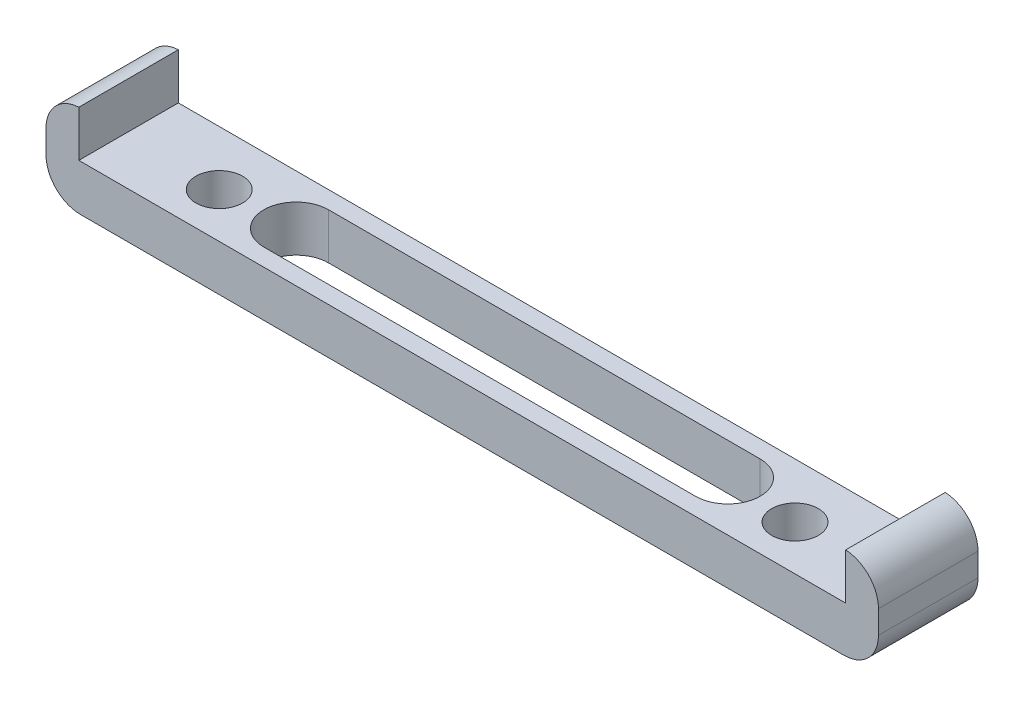
SolidWorks part; units mm, degrees
ref_plane "Front Plane" through (0, 0, 0) normal (0, 0, 1) x (1, 0, 0)
ref_plane "Top Plane" through (0, 0, 0) normal (0, 1, 0) x (1, 0, 0)
ref_plane "Right Plane" through (0, 0, 0) normal (1, 0, 0) x (0, 0, -1)
sketch "Sketch1" plane through (0, 0, 0) normal (0, 1, 0) x (1, 0, 0)
  line L0 (0, 0) -> (66.29, 0)
  line L1 (66.29, 0) -> (66.29, 100)
  line L2 (66.29, 100) -> (0, 100)
  line L3 (0, 100) -> (0, 0)
extrude "Boss-Extrude1" add sketch "Sketch1" along normal blind 41.59
shell "Shell2" thickness 3
sketch "Sketch3" plane through (0, 0, 0) normal (0, 0, 1) x (1, 0, 0)
  line L1 (0, 41.59) -> (66.29, 41.59) construction
  line L2 (54.395, 15) -> (11.895, 15)
  line L3 (11.895, 15) -> (11.895, 31.32)
  line L4 (11.895, 31.32) -> (8.815, 31.32)
  line L5 (8.815, 31.32) -> (8.815, 33.97)
  line L8 (7.145, 35.32) -> (7.755, 35.32)
  line L9 (7.755, 35.32) -> (8.815, 33.97)
  line L10 (7.145, 35.32) -> (7.145, 41.59)
  line L11 (7.145, 41.59) -> (59.145, 41.59)
  line L12 (57.145, 35.32) -> (59.145, 41.59)
  line L13 (57.145, 35.32) -> (56.535, 35.32)
  line L14 (56.535, 35.32) -> (55.475, 33.97)
  line L15 (55.475, 31.32) -> (55.475, 33.97)
  line L16 (52.395, 31.32) -> (55.475, 31.32)
  line L17 (54.395, 15) -> (52.395, 31.32)
  line L18 (33.145, 15) -> (33.145, 41.59) construction
  line L23 (0, 0) -> (66.29, 0)
  line L24 (66.29, 0) -> (66.29, 41.59)
  line L25 (66.29, 41.59) -> (0, 41.59)
  line L26 (0, 41.59) -> (0, 0)
  line L27 (0, 0) -> (66.29, 0) construction
  line L28 (66.29, 0) -> (66.29, 41.59) construction
  line L29 (66.29, 41.59) -> (0, 41.59) construction
  line L30 (0, 41.59) -> (0, 0) construction
  point P0 (33.145, 41.59)
  point P1 (33.145, 15)
  point P22 (33.145, 0)
  dimension "D1" = 16.32
  dimension "D2" = 21.25
  dimension "D3" = 0
  dimension "D4" = 2.65
  dimension "D5" = 1.35
  dimension "D6" = 1.06
  dimension "D7" = 0.61
  dimension "D8" = 3.08
  dimension "D9" = 26.59
extrude "Cut-Extrude1" cut sketch "Sketch3" against normal blind 125.59
fillet "Fillet1" radius 2 8 edges at (33.145, 0, 0) (33.145, 0, -100) (0, 20.795, -100) (66.29, 20.795, -100) (0, 20.795, 0) (66.29, 20.795, 0) (66.29, 0, -50) (0, 0, -50)
sketch "Sketch5" plane through (0, 0, 0) normal (-1, 0, 0) x (0, 0, 1)
  line L0 (-98, 0) -> (-2, 0) construction
  line L1 (-72.87, 8) -> (-90.37, 8) construction
  line L2 (-100, 8) -> (-72.87, 8) construction
  line L3 (-100, 2) -> (-100, 41.59) construction
  line L5 (-90.37, 8) -> (-90.37, 15.93) construction
  line L6 (-72.87, 8) -> (-72.87, 19.0845) construction
  circle A0 centre (-72.87, 8) radius 5
  circle A1 centre (-90.37, 15.93) radius 2.32
  circle A2 centre (-55.37, 15.93) radius 2.32
  dimension "D3" = 17.5
  dimension "D1" = 8
  dimension "D2" = 27.13
extrude "Cut-Extrude2" cut sketch "Sketch5" against normal up to surface (66.29 mm away) contours A0 | A1 | A2 up to face at (66.29, 21.795, -50)
sketch "Sketch6" plane through (0, 0, 0) normal (-1, 0, 0) x (0, 0, 1)
  line L0 (-72.87, 8) -> (-72.87, 0) construction
  line L1 (-98, 0) -> (-2, 0) construction
  line L2 (-72.87, 0) -> (-72.87, 25.24) construction
  circle A0 centre (-72.87, 25.24) radius 23.17
extrude "Cut-Extrude3" cut sketch "Sketch6" along direction (1, 0, 0) on the side against the normal up to surface (60.29 mm away) from offset 3 contours A0 offset against normal yes
sketch "Sketch7" plane through (0, 0, 0) normal (-1, 0, 0) x (0, 0, 1)
  circle A0 centre (-55.37, 15.93) radius 3.7
  circle A1 centre (-90.37, 15.93) radius 3.7
extrude "Cut-Extrude4" cut sketch "Sketch7" against normal blind 1 contours A1 | A0
ref_plane "Plane1" through (33.145, 0, 0) normal (-1, 0, 0) x (0, 0, 1)
sketch "Sketch8" plane through (0, 3, 0) normal (0, 1, 0) x (1, 0, 0)
  line L0 (3, 2) -> (3, 21.25)
  line L1 (3, 66.3714) -> (3, 2) construction
  line L2 (3, 21.25) -> (15.79, 21.25) construction
  line L3 (15.79, 21.25) -> (15.79, 18.5)
  line L4 (15.79, 18.5) -> (13, 18.5)
  line L5 (13, 18.5) -> (13, 2)
  line L6 (3, 2) -> (63.29, 2) construction
  line L7 (15.79, 21.25) -> (8, 21.25)
  line L8 (8, 21.25) -> (8, 18.5)
  line L9 (8, 18.5) -> (3, 18.5)
  line L10 (3, 2) -> (13, 2)
  line M9 (3, 2) -> (63.29, 2)
  dimension "D1" = 12.79
  dimension "D2" = 2.79
  dimension "D3" = 2.75
  dimension "D4" = 7.79
  dimension "D5" = 16.5
extrude "Boss-Extrude2" add sketch "Sketch8" along normal blind 10 contours L8 L9 L0 L5 L4 L3 L7 M9
sketch "Sketch9" plane through (0, 0, 0) normal (-1, 0, 0) x (0, 0, 1)
  line L0 (0, 8) -> (-8.24, 8) construction
  line L1 (-8.24, 0) -> (-8.24, 8) construction
  line L2 (-98, 0) -> (-2, 0) construction
  circle A0 centre (-8.24, 8) radius 1.5
  dimension "D1" = 8.24
  dimension "D2" = 8
extrude "Cut-Extrude5" cut sketch "Sketch9" against normal up to surface (13 mm away) up to face at (13, 8, -10.25)
sketch "Sketch10" plane through (13, 0, 0) normal (1, 0, 0) x (0, 0, -1)
  line L1 (11.24, 8) -> (9.74, 10.5981)
  line L2 (9.74, 10.5981) -> (6.74, 10.5981)
  line L3 (6.74, 10.5981) -> (5.24, 8)
  line L4 (2, 3) -> (18.5, 3)
  line L5 (18.5, 3) -> (18.5, 13)
  line L6 (18.5, 13) -> (2, 13)
  line L7 (2, 13) -> (2, 3)
  line L8 (2, 3) -> (18.5, 3)
  line L9 (18.5, 3) -> (18.5, 13)
  line L10 (18.5, 13) -> (2, 13)
  line L11 (2, 13) -> (2, 3)
  line L12 (5.24, 8) -> (6.74, 5.4019)
  line L13 (6.74, 5.4019) -> (9.74, 5.4019)
  line L14 (9.74, 5.4019) -> (11.24, 8)
  circle A0 centre (8.24, 8) radius 1.5 construction
  circle A1 centre (8.24, 8) radius 1.5
  circle A2 centre (8.24, 8) radius 2.5981 construction
  circle M6 centre (8.24, 8) radius 1.5
  dimension "D2" = 3
  dimension "D1" = 0
extrude "Cut-Extrude6" cut sketch "Sketch10" against normal blind 6 contours L13 L14 L1 L2 L3 L12 M6 | M6
chamfer "Chamfer1" distance 1 angle 45 11 edges at (13, 8, -2) (3, 8, -18.5) (8, 8, -18.5) (11.895, 13, -21.25) (15.79, 13, -19.875) (14.395, 13, -18.5) (13, 13, -10.25) (8, 13, -2) (3, 13, -10.25) (5.5, 13, -18.5) (8, 13, -19.875)
sketch "Sketch11" plane through (0, 3, 0) normal (0, 1, 0) x (1, 0, 0)
  line L0 (8, 21.25) -> (15.79, 21.25) construction
  line L1 (8, 52.25) -> (20.582, 52.25)
  line L2 (8, 52.25) -> (3, 52.25)
  line L3 (3, 98) -> (3, 2) construction
  line L4 (3, 55.3573) -> (20.582, 55.3573)
  line L5 (20.582, 55.3573) -> (20.582, 52.25)
  line L6 (3, 52.25) -> (3, 55.3573)
  dimension "D1" = 31
extrude "Boss-Extrude3" add sketch "Sketch11" along normal blind 7
chamfer "Chamfer2" distance 1 angle 45 3 edges at (11.791, 10, -55.3573) (20.582, 10, -53.8037) (11.791, 10, -52.25)
sketch "Sketch12" plane through (0, 41.59, 0) normal (0, 1, 0) x (1, 0, 0)
  line L0 (31.145, 63.43) -> (2.145, 63.43) construction
  line L1 (8.145, 13.1747) -> (33.145, 13.1747)
  line L2 (2.145, 63.43) -> (2.145, 8.43) construction
  line L3 (-3, 13.1747) -> (-3, 4.53)
  line L4 (4.5557, 2) -> (4.5557, 6) construction
  line L5 (33.145, 13.1747) -> (33.145, 4.53)
  line L6 (12, 2) -> (3, 2) construction
  line L7 (8.145, 13.1747) -> (-3, 13.1747)
  line L9 (8.145, 4.53) -> (-3, 4.53)
  line L10 (6.12, 8.43) -> (8.145, 8.43)
  line L11 (8.145, 4.53) -> (8.145, 2) construction
  line L12 (2.145, 35.93) -> (36.7413, 35.93) construction
  line L13 (8.145, 58.6853) -> (-3, 58.6853)
  line L14 (8.145, 67.33) -> (-3, 67.33)
  line L15 (-3, 58.6853) -> (-3, 67.33)
  line L16 (33.145, 4.53) -> (8.145, 4.53)
  line L17 (8.145, 58.6853) -> (33.145, 58.6853)
  line L18 (33.145, 58.6853) -> (33.145, 67.33)
  line L19 (33.145, 67.33) -> (8.145, 67.33)
  line L20 (15.6891, 79.3686) -> (15.6891, 66.3714)
  line L21 (63.29, 79.3686) -> (3, 79.3686) construction
  line L22 (3, 66.3714) -> (63.29, 66.3714) construction
  line L23 (15.6891, 66.3714) -> (15.6891, 72.87)
  line L24 (15.6891, 72.87) -> (15.6891, 63.62)
  line L25 (33.145, 0) -> (33.145, 103.586)
  line L26 (11.895, 0) -> (54.395, 0) construction
  line L27 (0, 98) -> (0, 2) construction
  circle A0 centre (8.145, 8.43) radius 2.025
  circle A2 centre (8.145, 63.43) radius 2.025
  dimension "D3" = 2.53
  dimension "D4" = 25
  dimension "D1" = 29
  dimension "D2" = 55
  dimension "D5" = 3
extrude "Boss-Extrude4" add sketch "Sketch12" against normal blind 4
mirror "Mirror1" about plane through (33.145, 0, 0) normal (-1, 0, 0) of "Boss-Extrude4", "Chamfer1", "Cut-Extrude4", "Boss-Extrude3", "Boss-Extrude2", "Cut-Extrude6", "Cut-Extrude5", "Chamfer2"
sketch "Sketch13" plane through (66.29, 0, 0) normal (1, 0, 0) x (0, 0, -1)
  line L0 (2, 41.59) -> (4.53, 41.59) construction
  line L1 (15.839, 41.3714) -> (26.3606, 23.5847)
  line L2 (26.3606, 23.5847) -> (47.0252, 23.8032)
  line L3 (47.0252, 23.8032) -> (57.1682, 41.8086)
  line L4 (57.1682, 41.8086) -> (46.6466, 59.5953)
  line L5 (46.6466, 59.5953) -> (25.982, 59.3768)
  line L6 (25.982, 59.3768) -> (15.839, 41.3714)
  line L8 (73.2417, 41.59) -> (78.5986, 32.3115)
  line L9 (78.5986, 32.3115) -> (89.3125, 32.3115)
  line L10 (89.3125, 32.3115) -> (94.6694, 41.59)
  line L11 (94.6694, 41.59) -> (89.3125, 50.8685)
  line L12 (89.3125, 50.8685) -> (78.5986, 50.8685)
  line L13 (78.5986, 50.8685) -> (73.2417, 41.59)
  circle A0 centre (36.5036, 41.59) radius 17.8971 construction
  circle A1 centre (83.9555, 41.59) radius 9.2785 construction
extrude "Cut-Extrude7" cut sketch "Sketch13" against normal up to surface (66.29 mm away) up to face at (0, 8, -6.74)
sketch "Sketch16" plane through (0, 41.59, 0) normal (0, 1, 0) x (1, 0, 0)
  line L0 (3, 67.33) -> (0, 67.33)
  line L1 (0, 73.2417) -> (0, 67.33) construction
  line L2 (0, 67.33) -> (0, 67.53)
  line L3 (0, 67.53) -> (3, 67.53)
  line L4 (3, 66.3714) -> (3, 79.3686) construction
  line L5 (3, 67.53) -> (3, 67.33)
  line L6 (12.4548, 63.0077) -> (2.2471, 63.0077) construction
  line L8 (3, 58.4853) -> (3, 58.6853)
  line L9 (0, 58.4853) -> (3, 58.4853)
  line L10 (0, 58.6853) -> (0, 58.4853)
  line L11 (3, 58.6853) -> (0, 58.6853)
  line L12 (12, 13.1747) -> (12.4548, 58.6853) construction
  line L13 (12.2274, 35.93) -> (6.6963, 35.93) construction
  line L14 (33.145, 0) -> (33.145, 51.8367) construction
  line L15 (11.895, 0) -> (54.395, 0) construction
  line L16 (3, 4.33) -> (3, 4.53)
  line L17 (0, 4.33) -> (3, 4.33)
  line L18 (0, 4.53) -> (0, 4.33)
  line L19 (3, 4.53) -> (0, 4.53)
  line L20 (3, 13.1747) -> (0, 13.1747)
  line L21 (0, 13.1747) -> (0, 13.3747)
  line L22 (0, 13.3747) -> (3, 13.3747)
  line L23 (3, 13.3747) -> (3, 13.1747)
  line L24 (63.29, 13.3747) -> (63.29, 13.1747)
  line L25 (66.29, 13.3747) -> (63.29, 13.3747)
  line L26 (66.29, 13.1747) -> (66.29, 13.3747)
  line L27 (63.29, 13.1747) -> (66.29, 13.1747)
  line L28 (63.29, 4.53) -> (66.29, 4.53)
  line L29 (66.29, 4.53) -> (66.29, 4.33)
  line L30 (66.29, 4.33) -> (63.29, 4.33)
  line L31 (63.29, 4.33) -> (63.29, 4.53)
  line L32 (63.29, 58.6853) -> (66.29, 58.6853)
  line L33 (66.29, 58.6853) -> (66.29, 58.4853)
  line L34 (66.29, 58.4853) -> (63.29, 58.4853)
  line L35 (63.29, 58.4853) -> (63.29, 58.6853)
  line L36 (63.29, 67.53) -> (63.29, 67.33)
  line L37 (66.29, 67.53) -> (63.29, 67.53)
  line L38 (66.29, 67.33) -> (66.29, 67.53)
  line L39 (63.29, 67.33) -> (66.29, 67.33)
  line L40 (12, 3) -> (12, 19.5) construction
  line L41 (3, 13.1747) -> (63.29, 13.1747) construction
extrude "Cut-Extrude8" cut sketch "Sketch16" against normal blind 4.2
sketch "Sketch17" plane through (0, 0, 0) normal (-1, 0, 0) x (0, 0, 1)
  line L0 (-67.53, 37.39) -> (-58.4853, 37.39)
  line L1 (-58.4853, 37.39) -> (-58.4853, 37.59)
  line L2 (-58.4853, 37.59) -> (-67.53, 37.59)
  line L3 (-67.53, 37.39) -> (-67.53, 41.59) construction
  line L4 (-67.53, 37.59) -> (-67.53, 37.39)
  line L5 (-58.6853, 41.59) -> (-13.1747, 41.59) construction
  line L6 (-35.93, 41.59) -> (-35.93, 36.3295) construction
  line L7 (-4.33, 37.59) -> (-4.33, 37.39)
  line L8 (-13.3747, 37.59) -> (-4.33, 37.59)
  line L9 (-13.3747, 37.39) -> (-13.3747, 37.59)
  line L10 (-4.33, 37.39) -> (-13.3747, 37.39)
extrude "Cut-Extrude9" cut sketch "Sketch17" against normal up to surface (66.29 mm away) up to face at (66.29, 35.2677, -43.8943)
delete or keep bodies "Body-Delete/Keep 2" type delete bodies bodies 114 115
sketch "Sketch18" plane through (0, 41.59, 0) normal (0, 1, 0) x (1, 0, 0)
  line L0 (69.29, 4.53) -> (-3, 4.53) construction
  line L1 (-3, 13.1747) -> (-0.15, 13.1747)
  line L2 (-3, 13.1747) -> (-3, 4.53)
  line L3 (-3, 4.53) -> (-0.15, 4.53)
  line L4 (-0.15, 13.1747) -> (-0.15, 4.53)
  line L6 (69.29, 13.1747) -> (66.44, 13.1747)
  line L7 (69.29, 13.1747) -> (69.29, 4.53)
  line L8 (69.29, 4.53) -> (66.44, 4.53)
  line L9 (66.44, 13.1747) -> (66.44, 4.53)
  dimension "D1" = 2.85
  dimension "D2" = 2.85
extrude "Boss-Extrude5" add sketch "Sketch18" along normal blind 4
fillet "Fillet2" radius 3 8 edges at (-3, 37.59, -8.8523) (69.29, 37.59, -8.8523) (-3, 45.59, -8.8523) (-1.575, 45.59, -4.53) (-1.575, 45.59, -13.1747) (69.29, 45.59, -8.8523) (67.865, 45.59, -13.1747) (67.865, 45.59, -4.53)
sketch "Sketch19" plane through (0, 41.59, 0) normal (0, 1, 0) x (1, 0, 0)
  line L0 (8.145, 8.8523) -> (58.145, 8.8523) construction
  line L1 (33.145, 8.8523) -> (33.145, 12.5118) construction
  line L2 (14.4028, 11.6605) -> (51.8872, 11.6605)
  line L3 (14.4028, 6.0442) -> (51.8872, 6.0442)
  line L4 (-0.15, 13.1747) -> (-0.15, 4.53) construction
  arc A0 (14.4028, 11.6605) -> (14.4028, 6.0442) centre (14.4028, 8.8523) ccw
  arc A1 (51.8872, 11.6605) -> (51.8872, 6.0442) centre (51.8872, 8.8523) cw
  point P5 (-0.15, 8.8523)
extrude "Cut-Extrude10" cut sketch "Sketch19" against normal blind 10
